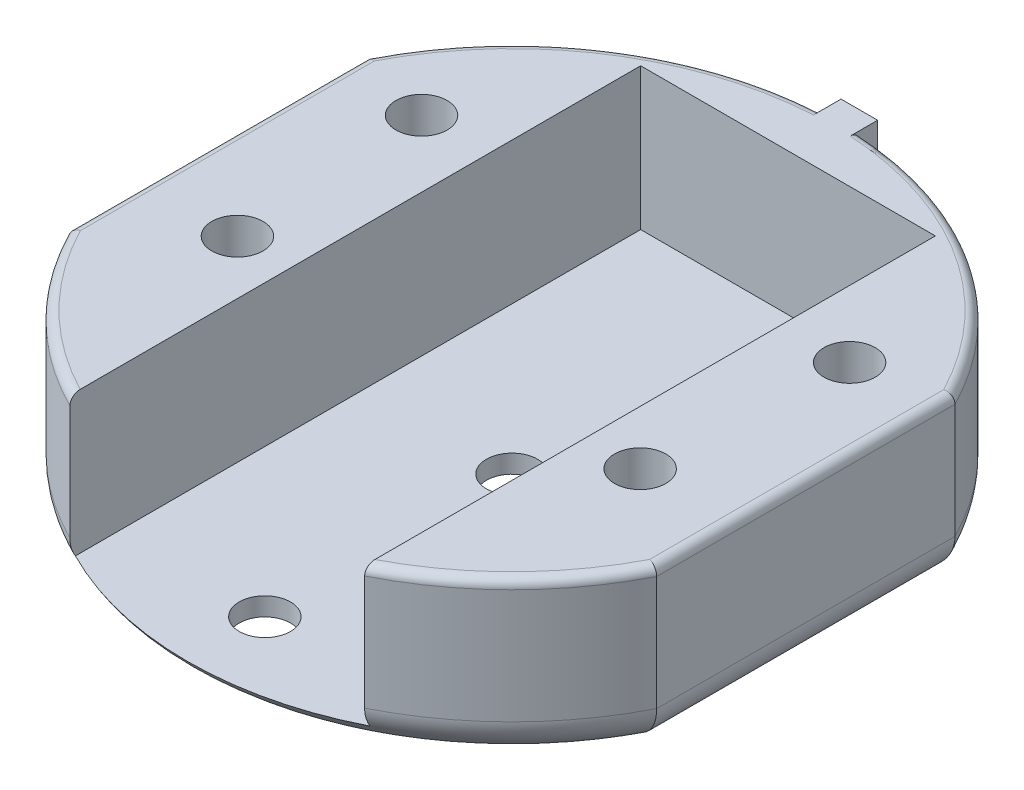
SolidWorks part; units mm, degrees
ref_plane "Front Plane" through (0, 0, 0) normal (0, 0, 1) x (1, 0, 0)
ref_plane "Top Plane" through (0, 0, 0) normal (0, 1, 0) x (1, 0, 0)
ref_plane "Right Plane" through (0, 0, 0) normal (1, 0, 0) x (0, 0, -1)
sketch "Sketch1" plane through (0, 0, 0) normal (0, 1, 0) x (1, 0, 0)
  line L0 (-1, 17.9722) -> (-1, 18.9722)
  line L1 (-1, 18.9722) -> (1, 18.9722)
  line L2 (1, 18.9722) -> (1, 17.9722)
  line L3 (0, 18.9722) -> (0, 0) construction
  arc A0 (-1, 17.9722) -> (1, 17.9722) centre (0, 0) ccw
  dimension "D1" = 36
  dimension "D2" = 2
  dimension "D3" = 1
extrude "Boss-Extrude1" add sketch "Sketch1" along normal blind 1
sketch "Sketch2" plane through (0, 0, 0) normal (0, 0, 1) x (1, 0, 0)
  line L0 (18, 1) -> (-18, 1) construction
  line L1 (0, 8.95) -> (-10.9803, 8.95) construction
  line L2 (-16.05, 8.75) -> (-8.05, 8.75)
  line L3 (-16.05, 8.75) -> (-16.05, 1)
  line L4 (8.05, 8.75) -> (16.05, 8.75)
  line L5 (16.05, 8.75) -> (16.05, 1)
  line L6 (0, 8.95) -> (0, 0) construction
  line L8 (-8.05, 8.75) -> (-8.05, 1)
  line L9 (-7.95, 1) -> (7.95, 1) construction
  line L10 (-7.95, 1) -> (-7.95, 16.9) construction
  line L11 (-7.95, 16.9) -> (7.95, 16.9) construction
  line L12 (7.95, 1) -> (7.95, 16.9) construction
  line L13 (-7.95, 1) -> (7.95, 16.9) construction
  line L14 (-7.95, 16.9) -> (7.95, 1) construction
  line L16 (8.05, 8.75) -> (8.05, 1)
  line L17 (-8.05, 1) -> (-16.05, 1)
  line L18 (16.05, 1) -> (8.05, 1)
  dimension "D1" = 15.9
  dimension "D2" = 0.1
  dimension "D3" = 0.1
  dimension "D4" = 0.2
  dimension "D5" = 8
extrude "Boss-Extrude2" add sketch "Sketch2" along normal through all and the other way through all
sketch "Sketch3" plane through (0, 0, 0) normal (0, -1, 0) x (1, 0, 0)
  line L3 (-1, -17.9722) -> (-1, -18.9722)
  line L4 (-1, -18.9722) -> (1, -18.9722)
  line L5 (1, -18.9722) -> (1, -17.9722)
  line L6 (-1, -17.9722) -> (-1, -18.9722)
  line L7 (-1, -18.9722) -> (1, -18.9722)
  line L8 (1, -18.9722) -> (1, -17.9722)
  circle A0 centre (0, 0) radius 59.9105
  arc A1 (1, -17.9722) -> (-1, -17.9722) centre (0, 0) ccw
  arc A2 (1, -17.9722) -> (-1, -17.9722) centre (0, 0) ccw
  dimension "D1" = 0
extrude "Cut-Extrude1" cut sketch "Sketch3" against normal through all
sketch "Sketch5" plane through (0, 0, 0) normal (0, 1, 0) x (1, 0, 0)
  line L0 (-11, -4) -> (11, -4) construction
  line L1 (0, -4) -> (0, 0) construction
  circle A0 centre (0, 0) radius 1.4
  circle A2 centre (11, -4) radius 1.4
  circle A4 centre (-11, -4) radius 1.4
  arc A6 (0, -14.525) -> (0, -12.475) centre (0, -13.5) ccw construction
  arc A7 (-11.6913, 7.775) -> (-11.6913, 5.725) centre (-11.6913, 6.75) ccw construction
  arc A8 (0, -14.525) -> (0, -12.475) centre (0, -13.5) ccw construction
  arc A9 (11.6913, 5.725) -> (11.6913, 7.775) centre (11.6913, 6.75) ccw construction
  arc A10 (-11.6913, 7.775) -> (-11.6913, 5.725) centre (-11.6913, 6.75) ccw construction
  arc A11 (11.6913, 5.725) -> (11.6913, 7.775) centre (11.6913, 6.75) ccw construction
  circle A13 centre (-11.6913, 6.75) radius 1.4
  circle A15 centre (0, -13.5) radius 1.4
  circle A17 centre (11.6913, 6.75) radius 1.4
  dimension "D1" = 2.8
  dimension "D2" = 2.8
  dimension "D3" = 22
  dimension "D4" = 4
extrude "Cut-Extrude2" cut sketch "Sketch5" against normal through all and the other way through all
sketch "Sketch6" plane through (0, 0, 0) normal (0, -1, 0) x (1, 0, 0)
  line L0 (-8.0975, -15.0758) -> (8.0975, -15.0758)
  line L4 (-8.0975, -15.0758) -> (-8.0975, -16.0758)
  line L5 (8.0975, -15.0758) -> (8.0975, -16.0758)
  line L17 (1, -18.9722) -> (1, -17.9722)
  line L18 (-1, -18.9722) -> (1, -18.9722)
  line L19 (-1, -17.9722) -> (-1, -18.9722)
  arc A7 (1, -17.9722) -> (8.0975, -16.0758) centre (0, 0) ccw
  arc A8 (-8.0975, -16.0758) -> (-1, -17.9722) centre (0, 0) ccw
  dimension "D1" = 1
extrude "Boss-Extrude3" add sketch "Sketch6" against normal up to surface (8.75 mm away) up to face at (-13.0913, 8.75, -6.75)
sketch "Sketch7" plane through (0, 1, 0) normal (0, 1, 0) x (1, 0, 0)
  line L0 (16.05, 8.1485) -> (16.05, -8.1485) construction
  line L1 (-16.05, -8.1485) -> (-16.05, 8.1485) construction
  line L2 (16.05, 8.1485) -> (16.05, -8.1485)
  line L3 (-16.05, -8.1485) -> (-16.05, 8.1485)
  arc A0 (16.05, -8.1485) -> (16.05, 8.1485) centre (0, 0) ccw construction
  arc A1 (-16.05, 8.1485) -> (-16.05, -8.1485) centre (0, 0) ccw construction
  arc A2 (16.05, -8.1485) -> (16.05, 8.1485) centre (0, 0) ccw
  arc A3 (-16.05, 8.1485) -> (-16.05, -8.1485) centre (0, 0) ccw
extrude "Cut-Extrude3" cut sketch "Sketch7" against normal through all
fillet "Fillet1" radius 2 5 edges at (16.05, 0, 0) (-16.05, 0, 0) (0, 0, 18) (9.8388, 0, -15.0731) (-9.8388, 0, -15.0731)
fillet "Fillet2" radius 0.5 6 edges at (-9.8388, 8.75, -15.0731) (12.6889, 8.75, 12.7668) (16.05, 8.75, 0) (-16.05, 8.75, 0) (9.8388, 8.75, -15.0731) (-12.6889, 8.75, 12.7668)
